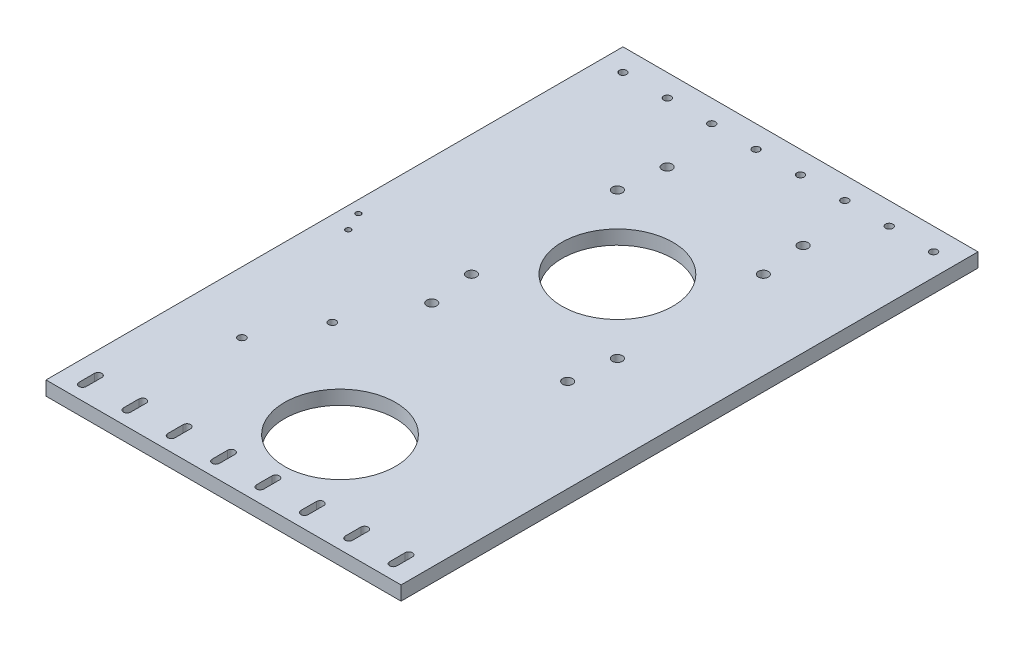
SolidWorks part; units mm, degrees
material "6061 Alloy"
ref_plane "Front Plane" through (0, 0, 0) normal (0, 0, 1) x (1, 0, 0)
ref_plane "Top Plane" through (0, 0, 0) normal (0, 1, 0) x (1, 0, 0)
ref_plane "Right Plane" through (0, 0, 0) normal (1, 0, 0) x (0, 0, -1)
sketch "Sketch1" plane through (0, 0, 0) normal (0, 1, 0) x (1, 0, 0)
  line L0 (87.5, 260) -> (87.5, 0) construction
  line L1 (0, 0) -> (160, 0)
  line L2 (0, 0) -> (0, 260)
  line L3 (0, 260) -> (160, 260)
  line L4 (160, 0) -> (160, 260)
  line L5 (56.875, 223.0441) -> (118.125, 223.0441) construction
  line L6 (10, 6.5) -> (10, 13.5) construction
  line L7 (5.4755, 135.2989) -> (9.5163, 126.7011) construction
  line L8 (22, 0) -> (22, 260) construction
  line L9 (22, 136) -> (0, 136) construction
  line L10 (22, 126) -> (0, 126) construction
  line L11 (0, 136) -> (0, 126) construction
  line L12 (17.3003, 136) -> (22, 126) construction
  line L13 (8.35, 6.5) -> (8.35, 13.5)
  line L14 (11.65, 6.5) -> (11.65, 13.5)
  line L15 (10, 250) -> (10, 0) construction
  line L16 (31.65, 6.5) -> (31.65, 13.5)
  line L17 (28.35, 6.5) -> (28.35, 13.5)
  line L18 (30, 6.5) -> (30, 13.5) construction
  line L19 (51.65, 6.5) -> (51.65, 13.5)
  line L20 (48.35, 6.5) -> (48.35, 13.5)
  line L21 (50, 6.5) -> (50, 13.5) construction
  line L22 (71.65, 6.5) -> (71.65, 13.5)
  line L23 (68.35, 6.5) -> (68.35, 13.5)
  line L24 (70, 6.5) -> (70, 13.5) construction
  line L25 (91.65, 6.5) -> (91.65, 13.5)
  line L26 (88.35, 6.5) -> (88.35, 13.5)
  line L27 (90, 6.5) -> (90, 13.5) construction
  line L28 (111.65, 6.5) -> (111.65, 13.5)
  line L29 (108.35, 6.5) -> (108.35, 13.5)
  line L30 (110, 6.5) -> (110, 13.5) construction
  line L31 (131.65, 6.5) -> (131.65, 13.5)
  line L32 (128.35, 6.5) -> (128.35, 13.5)
  line L33 (130, 6.5) -> (130, 13.5) construction
  line L34 (151.65, 6.5) -> (151.65, 13.5)
  line L35 (148.35, 6.5) -> (148.35, 13.5)
  line L36 (150, 6.5) -> (150, 13.5) construction
  line L37 (10, 250) -> (30, 250) construction
  line L38 (118.125, 223.0441) -> (118.125, 116.9559) construction
  line L39 (118.125, 116.9559) -> (56.875, 116.9559) construction
  line L40 (56.875, 116.9559) -> (56.875, 223.0441) construction
  circle A0 centre (87.5, 170) radius 25
  circle A1 centre (87.5, 45) radius 25
  circle A2 centre (87.5, 170) radius 61.25 construction
  circle A4 centre (118.125, 116.9559) radius 2.25
  circle A5 centre (56.875, 116.9559) radius 2.25
  circle A7 centre (56.875, 223.0441) radius 2.25
  circle A8 centre (118.125, 223.0441) radius 2.25
  circle A10 centre (5.4755, 135.2989) radius 1.175
  circle A11 centre (9.5163, 126.7011) radius 1.175
  circle A12 centre (87.5, 170) radius 78 construction
  circle A13 centre (10, 250) radius 1.65
  arc A14 (8.35, 6.5) -> (11.65, 6.5) centre (10, 6.5) ccw
  arc A15 (11.65, 13.5) -> (8.35, 13.5) centre (10, 13.5) ccw
  circle A16 centre (30, 250) radius 1.65
  arc A17 (28.35, 6.5) -> (31.65, 6.5) centre (30, 6.5) ccw
  arc A18 (31.65, 13.5) -> (28.35, 13.5) centre (30, 13.5) ccw
  circle A19 centre (50, 250) radius 1.65
  arc A20 (48.35, 6.5) -> (51.65, 6.5) centre (50, 6.5) ccw
  arc A21 (51.65, 13.5) -> (48.35, 13.5) centre (50, 13.5) ccw
  circle A22 centre (70, 250) radius 1.65
  arc A23 (68.35, 6.5) -> (71.65, 6.5) centre (70, 6.5) ccw
  arc A24 (71.65, 13.5) -> (68.35, 13.5) centre (70, 13.5) ccw
  circle A25 centre (90, 250) radius 1.65
  arc A26 (88.35, 6.5) -> (91.65, 6.5) centre (90, 6.5) ccw
  arc A27 (91.65, 13.5) -> (88.35, 13.5) centre (90, 13.5) ccw
  circle A28 centre (110, 250) radius 1.65
  arc A29 (108.35, 6.5) -> (111.65, 6.5) centre (110, 6.5) ccw
  arc A30 (111.65, 13.5) -> (108.35, 13.5) centre (110, 13.5) ccw
  circle A31 centre (130, 250) radius 1.65
  arc A32 (128.35, 6.5) -> (131.65, 6.5) centre (130, 6.5) ccw
  arc A33 (131.65, 13.5) -> (128.35, 13.5) centre (130, 13.5) ccw
  circle A34 centre (150, 250) radius 1.65
  arc A35 (148.35, 6.5) -> (151.65, 6.5) centre (150, 6.5) ccw
  arc A36 (151.65, 13.5) -> (148.35, 13.5) centre (150, 13.5) ccw
  point P15 (87.5, 170)
  point P29 (10, 10)
  point P42 (7.4959, 131)
  point P43 (0, 131)
  point P55 (30, 10)
  point P65 (50, 10)
  point P74 (70, 10)
  point P83 (90, 10)
  point P92 (110, 10)
  point P101 (130, 10)
  point P110 (150, 10)
  dimension "D3" = 50
  dimension "D4" = 50
  dimension "D7" = 122.5
  dimension "D8" = 4.5
  dimension "D11" = 124
  dimension "D13" = 2.35
  dimension "D16" = 156
  dimension "D19" = 3.3
  dimension "D24" = 240
  dimension "D27" = 106.0881
  dimension "D1" = 160
  dimension "D2" = 260
  dimension "D5" = 125
  dimension "D6" = 90
  dimension "D10" = 56.875
  dimension "D12" = 65.5
  dimension "D14" = 9.5
  dimension "D15" = 10
  dimension "D17" = 11
  dimension "D18" = 72.5
  dimension "D20" = 10
  dimension "D21" = 10
  dimension "D22" = 3.3
  dimension "D23" = 7
  dimension "D26" = 20
  dimension "D9" = 36.9559
  dimension "D25" = 8
extrude "Boss-Extrude1" add sketch "Sketch1" along normal blind 6.35 contours A1 | A0 | A4 | A8 | A7 | L4 L3 L2 L1 | A5 | A11 | A10 | A28 | A25 | A31 | A34 | A22 | A19 | A16 | A13 | L14 A15 L13 A14 | L16 A18 L17 A17 | L19 A21 L20 A20 | L22 A24 L23 A23 | L25 A27 L26 A26 | L28 A30 L29 A29 | L31 A33 L32 A32 | L34 A36 L35 A35 region at (87.5, 0, -170) region at (87.5, 0, -45) region at (118.125, 0, -116.9559) region at (56.875, 0, -223.0441) region at (118.125, 0, -223.0441)
sketch "Sketch2" plane through (0, 6.35, 0) normal (0, 1, 0) x (1, 0, 0)
  line L0 (27.6639, 60.641) -> (42.0639, 86.959) construction
  line L1 (87.5, 170) -> (42.0639, 86.959) construction
  line L2 (34.8639, 73.8) -> (87.5, 45) construction
  circle A0 centre (27.6639, 60.641) radius 1.7
  circle A1 centre (42.0639, 86.959) radius 1.7
  dimension "D1" = 3.4
  dimension "D2" = 30
  dimension "D3" = 60
extrude "Cut-Extrude1" cut sketch "Sketch2" against normal through all
sketch "Sketch3" plane through (0, 6.35, 0) normal (0, 1, 0) x (1, 0, 0)
  line L1 (120.3805, 202.8805) -> (54.6195, 202.8805) construction
  line L2 (120.3805, 202.8805) -> (120.3805, 137.1195) construction
  line L3 (120.3805, 137.1195) -> (54.6195, 137.1195) construction
  line L4 (54.6195, 202.8805) -> (54.6195, 137.1195) construction
  circle A0 centre (54.6195, 202.8805) radius 2.25
  circle A1 centre (54.6195, 137.1195) radius 2.25
  circle A2 centre (120.3805, 137.1195) radius 2.25
  circle A3 centre (120.3805, 202.8805) radius 2.25
  point P8 (118.6127, 138.8873)
  point P9 (54.5787, 202.7289)
  point P10 (54.5353, 202.3857)
  point P11 (120.3805, 202.8805)
  point P12 (54.6195, 137.1195)
  point P13 (56.3873, 201.1127)
  point P14 (54.6195, 200.6305)
  point P15 (54.916, 201.1127)
  point P16 (118.6127, 202.9868)
  point P17 (55.0235, 202.8858)
  point P18 (54.5562, 202.3687)
  point P19 (54.6195, 202.8805)
  point P20 (120.2936, 137.1016)
  point P21 (120.3246, 137.1147)
  point P22 (121.2926, 139.1764)
  point P23 (120.4746, 137.283)
  point P24 (120.4056, 137.1534)
  point P25 (120.3805, 202.8805)
  point P26 (54.6195, 202.8805)
  point P28 (54.6195, 137.1195)
  dimension "D3" = 4.5
extrude "Cut-Extrude2" cut sketch "Sketch3" against normal up to next
